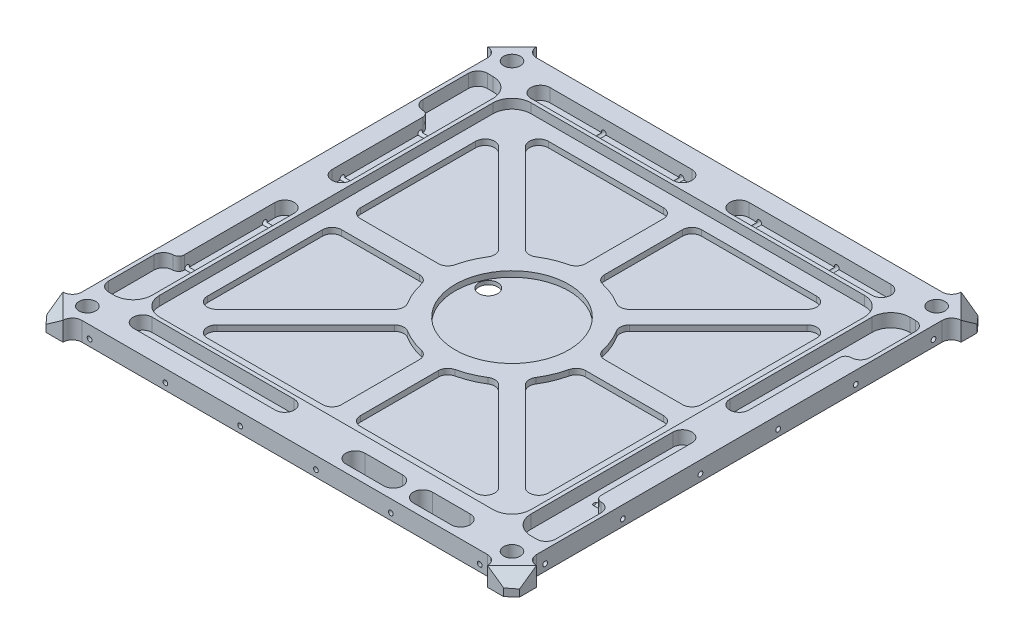
SolidWorks part; units mm, degrees
note: The reader was unsure of these and kept them because the rebuilt part matched: shared geometry of "Sketch2<6>".
ref_plane "Front" through (0, 0, 0) normal (0, 0, 1) x (1, 0, 0)
ref_plane "Top" through (0, 0, 0) normal (0, 1, 0) x (1, 0, 0)
ref_plane "Right" through (0, 0, 0) normal (1, 0, 0) x (0, 0, -1)
sketch "Sketch1" plane through (0, 0, 0) normal (0, 1, 0) x (1, 0, 0)
  line L0 (0, 125) -> (0, -125) construction
  line L1 (-125, 125) -> (125, 125)
  line L2 (-125, 125) -> (-125, -125)
  line L3 (-125, -125) -> (125, -125)
  line L4 (125, 125) -> (125, -125)
  line L5 (-125, 0) -> (125, 0) construction
  line L6 (-125, -125) -> (-112.08, -125)
  line L7 (-125, -125) -> (-125, -112.08)
  line L8 (-112.08, -125) -> (-107.08, -125)
  line L9 (-125, -125) -> (125, 125) construction
  line L10 (-125, -112.08) -> (-125, -107.08) construction
  line L11 (-107.08, -120) -> (107.08, -120)
  line L12 (-120, -107.08) -> (-120, 107.08)
  line L13 (120, -107.08) -> (120, 107.08)
  line L14 (-107.08, 120) -> (107.08, 120)
  line L15 (16.3873, 116) -> (82.4628, 116) construction
  line L16 (28.29, 116) -> (48.29, 116)
  line L17 (48.29, 111) -> (63.91, 111) construction
  line L18 (48.29, 106) -> (28.29, 106)
  line L19 (63.91, 106) -> (83.91, 106)
  line L20 (83.91, 116) -> (63.91, 116)
  line L21 (-125, 125) -> (125, -125) construction
  line L22 (-107.08, 120) -> (107.08, 120)
  line L23 (120, 107.08) -> (120, -107.08)
  line L24 (107.08, -120) -> (-107.08, -120)
  line L25 (-120, -107.08) -> (-120, 107.08)
  line L26 (63.91, -106) -> (83.91, -106)
  line L27 (83.91, -116) -> (63.91, -116)
  line L28 (28.29, -116) -> (48.29, -116)
  line L29 (48.29, -106) -> (28.29, -106)
  arc A0 (-112.08, -125) -> (-107.08, -120) centre (-107.08, -125) cw
  arc A1 (-125, -112.08) -> (-120, -107.08) centre (-125, -107.08) ccw
  arc A2 (112.08, -125) -> (107.08, -120) centre (107.08, -125) ccw
  arc A3 (125, -112.08) -> (120, -107.08) centre (125, -107.08) cw
  arc A4 (125, 112.08) -> (120, 107.08) centre (125, 107.08) ccw
  arc A5 (112.08, 125) -> (107.08, 120) centre (107.08, 125) cw
  arc A6 (-112.08, 125) -> (-107.08, 120) centre (-107.08, 125) ccw
  arc A7 (-125, 112.08) -> (-120, 107.08) centre (-125, 107.08) cw
  arc A8 (28.29, 116) -> (28.29, 106) centre (28.29, 111) ccw
  arc A9 (48.29, 106) -> (48.29, 116) centre (48.29, 111) ccw
  arc A10 (63.91, 116) -> (63.91, 106) centre (63.91, 111) ccw
  arc A11 (83.91, 106) -> (83.91, 116) centre (83.91, 111) ccw
  circle A12 centre (-22.5, 10) radius 5
  arc A13 (63.91, -116) -> (63.91, -106) centre (63.91, -111) cw
  arc A14 (83.91, -106) -> (83.91, -116) centre (83.91, -111) cw
  arc A15 (48.29, -106) -> (48.29, -116) centre (48.29, -111) cw
  arc A16 (28.29, -116) -> (28.29, -106) centre (28.29, -111) cw
  point P18 (0, -120)
  point P25 (120, 0)
  point P36 (-120, 0)
  point P50 (-112.0764, 112.0764)
  point P51 (112.0764, 112.0764)
  point P52 (112.0764, -112.0764)
  point P53 (-112.0764, -112.0764)
  dimension "D13" = 5
  dimension "D14" = 5
  dimension "D22" = 10
  dimension "D1" = 125
  dimension "D2" = 250
  dimension "D3" = 125
  dimension "D4" = 250
  dimension "D5" = 12.92
  dimension "D6" = 12.92
  dimension "D7" = 5
  dimension "D8" = 5
  dimension "D9" = 4
  dimension "D10" = 28.29
  dimension "D11" = 20
  dimension "D12" = 10
  dimension "D15" = 15.62
  dimension "D16" = 20
  dimension "D17" = 158.5
  dimension "D18" = 317
  dimension "D19" = 158.5
  dimension "D20" = 317
  dimension "D21" = 22.5
  dimension "D23" = 10
extrude "Boss-Extrude1" add sketch "Sketch1" along normal mid plane 10 contours L2 A7 L12 A1 L3 A0 L11 A2 L4 A3 L13 A4 L1 A5 L14 A6 A12 A11 L19 A10 L20 A9 L18 A8 L16 | L18 A9 L16 A8 | L19 A11 L20 A10
sketch "Sketch2" plane through (0, 5, 0) normal (0, -1, 0) x (1, 0, 0)
  line L0 (34.5597, 27.4887) -> (67.1751, 60.1041)
  line L1 (-5, 43.8748) -> (-5, 85)
  line L2 (27.4887, 34.5597) -> (60.1041, 67.1751)
  line L3 (5, 43.8748) -> (5, 85)
  line L4 (43.8748, -5) -> (85, -5)
  line L5 (43.8748, 5) -> (85, 5)
  line L6 (27.4887, -34.5597) -> (60.1041, -67.1751)
  line L7 (34.5597, -27.4887) -> (67.1751, -60.1041)
  line L8 (-5, -43.8748) -> (-5, -85)
  line L9 (5, -43.8748) -> (5, -85)
  line L10 (-34.5597, -27.4887) -> (-67.1751, -60.1041)
  line L11 (-27.4887, -34.5597) -> (-60.1041, -67.1751)
  line L12 (-43.8748, 5) -> (-85, 5)
  line L13 (-43.8748, -5) -> (-85, -5)
  line L14 (-27.4887, 34.5597) -> (-60.1041, 67.1751)
  line L15 (-34.5597, 27.4887) -> (-67.1751, 60.1041)
  line L16 (-88, 98) -> (88, 98)
  line L17 (-107.08, 120) -> (107.08, 120) construction
  line L18 (10, 90) -> (70.8579, 90)
  line L19 (-10, 90) -> (-70.8579, 90)
  line L20 (60.1041, 67.1751) -> (74.3934, 81.4645)
  line L21 (67.1751, 60.1041) -> (81.4645, 74.3934)
  line L22 (-60.1041, 67.1751) -> (-74.3934, 81.4645)
  line L23 (-67.1751, 60.1041) -> (-81.4645, 74.3934)
  line L24 (120, 107.08) -> (120, -107.08) construction
  line L25 (-120, 107.08) -> (-120, -107.08) construction
  line L26 (-98, 88) -> (-98, -88)
  line L27 (-60.1041, -67.1751) -> (-74.3934, -81.4645)
  line L28 (-90, 10) -> (-90, 70.8579)
  line L29 (-90, -10) -> (-90, -70.8579)
  line L30 (-67.1751, -60.1041) -> (-81.4645, -74.3934)
  line L31 (-88, -98) -> (88, -98)
  line L32 (98, -88) -> (98, 88)
  line L34 (-10, -90) -> (-70.8579, -90)
  line L35 (10, -90) -> (70.8579, -90)
  line L36 (90, -70.8579) -> (90, -10)
  line L37 (67.1751, -60.1041) -> (81.4645, -74.3934)
  line L38 (60.1041, -67.1751) -> (74.3934, -81.4645)
  line L39 (90, 10) -> (90, 70.8579)
  line L41 (-125, -125) -> (-125, -112.08) construction
  line L42 (-125, -125) -> (-112.08, -125) construction
  circle A0 centre (0, 0) radius 30
  arc A1 (-8.8889, 38.9998) -> (-21.2917, 33.8624) centre (0, 0) ccw
  arc A2 (5, 43.8748) -> (8.8889, 38.9998) centre (10, 43.8748) ccw
  arc A3 (-8.8889, 38.9998) -> (-5, 43.8748) centre (-10, 43.8748) ccw
  arc A4 (21.2917, 33.8624) -> (27.4887, 34.5597) centre (23.9531, 38.0953) ccw
  arc A5 (34.5597, 27.4887) -> (33.8624, 21.2917) centre (38.0953, 23.9531) ccw
  arc A6 (38.9998, 8.8889) -> (43.8748, 5) centre (43.8748, 10) ccw
  arc A7 (43.8748, -5) -> (38.9998, -8.8889) centre (43.8748, -10) ccw
  arc A8 (33.8624, -21.2917) -> (34.5597, -27.4887) centre (38.0953, -23.9531) ccw
  arc A9 (27.4887, -34.5597) -> (21.2917, -33.8624) centre (23.9531, -38.0953) ccw
  arc A10 (8.8889, -38.9998) -> (5, -43.8748) centre (10, -43.8748) ccw
  arc A11 (-5, -43.8748) -> (-8.8889, -38.9998) centre (-10, -43.8748) ccw
  arc A12 (-21.2917, -33.8624) -> (-27.4887, -34.5597) centre (-23.9531, -38.0953) ccw
  arc A13 (-34.5597, -27.4887) -> (-33.8624, -21.2917) centre (-38.0953, -23.9531) ccw
  arc A14 (-38.9998, -8.8889) -> (-43.8748, -5) centre (-43.8748, -10) ccw
  arc A15 (-43.8748, 5) -> (-38.9998, 8.8889) centre (-43.8748, 10) ccw
  arc A16 (-33.8624, 21.2917) -> (-34.5597, 27.4887) centre (-38.0953, 23.9531) ccw
  arc A17 (-27.4887, 34.5597) -> (-21.2917, 33.8624) centre (-23.9531, 38.0953) ccw
  arc A18 (-21.2917, -33.8624) -> (21.2917, -33.8624) centre (0, 0) ccw
  arc A19 (-38.9998, -8.8889) -> (-33.8624, -21.2917) centre (0, 0) ccw
  arc A20 (-33.8624, 21.2917) -> (-38.9998, 8.8889) centre (0, 0) ccw
  arc A21 (21.2917, 33.8624) -> (8.8889, 38.9998) centre (0, 0) ccw
  arc A22 (38.9998, 8.8889) -> (33.8624, 21.2917) centre (0, 0) ccw
  arc A23 (33.8624, -21.2917) -> (38.9998, -8.8889) centre (0, 0) ccw
  arc A24 (-85, -5) -> (-90, -10) centre (-85, -10) ccw
  arc A25 (-85, 5) -> (-90, 10) centre (-85, 10) cw
  arc A26 (-74.3934, 81.4645) -> (-70.8579, 90) centre (-70.8579, 85) cw
  arc A27 (-81.4645, 74.3934) -> (-90, 70.8579) centre (-85, 70.8579) ccw
  arc A28 (-5, 85) -> (-10, 90) centre (-10, 85) ccw
  arc A29 (5, 85) -> (10, 90) centre (10, 85) cw
  arc A30 (74.3934, 81.4645) -> (70.8579, 90) centre (70.8579, 85) ccw
  arc A31 (90, 70.8579) -> (81.4645, 74.3934) centre (85, 70.8579) ccw
  arc A32 (85, 5) -> (90, 10) centre (85, 10) ccw
  arc A33 (85, -5) -> (90, -10) centre (85, -10) cw
  arc A34 (81.4645, -74.3934) -> (90, -70.8579) centre (85, -70.8579) ccw
  arc A35 (74.3934, -81.4645) -> (70.8579, -90) centre (70.8579, -85) cw
  arc A36 (5, -85) -> (10, -90) centre (10, -85) ccw
  arc A37 (-5, -85) -> (-10, -90) centre (-10, -85) cw
  arc A38 (-81.4645, -74.3934) -> (-90, -70.8579) centre (-85, -70.8579) cw
  arc A39 (-74.3934, -81.4645) -> (-70.8579, -90) centre (-70.8579, -85) ccw
  arc A40 (-98, -88) -> (-88, -98) centre (-88, -88) ccw
  arc A41 (88, -98) -> (98, -88) centre (88, -88) ccw
  arc A42 (88, 98) -> (98, 88) centre (88, 88) cw
  arc A43 (-88, 98) -> (-98, 88) centre (-88, 88) ccw
  point P69 (0, 0)
  point P94 (-90, 5)
  point P101 (-5, 90)
  point P104 (5, 90)
  point P113 (90, -5)
  point P128 (-98, -98)
  point P131 (98, -98)
  point P134 (98, 98)
  point P137 (-98, 98)
  circle M131 centre (-22.5, -10) radius 5
  dimension "D1" = 60
  dimension "D2" = 80
  dimension "D5" = 10
  dimension "D6" = 10
  dimension "D9" = 8
  dimension "D15" = 5
  dimension "D18" = 10
  dimension "D3" = 10
  dimension "D4" = 5
  dimension "D7" = 8
  dimension "D8" = 22
  dimension "D10" = 8
  dimension "D11" = 196
  dimension "D12" = 22
  dimension "D13" = 22
  dimension "D14" = 22
  dimension "D16" = 8
  dimension "D17" = 8
extrude "Cut-Extrude3" cut sketch "Sketch2<6>" along normal blind 5 contours A43 L16 A42 L32 A41 L31 A40 L26 L5 A32 L39 A31 L21 L0 A5 A22 A6 L1 A28 L19 A26 L22 L14 A17 A1 A3 A0 L23 A27 L28 A25 L12 A15 A20 A16 L15 L20 A30 L18 A29 L3 A2 A21 A4 L2 | A27 L23 L15 A16 A20 A15 L12 A25 L28 | A28 L1 A3 A1 A17 L14 L22 A26 L19 | L30 A38 L29 A24 L13 A14 A19 A13 L10 | A39 L27 L11 A12 A18 A11 L8 A37 L34 | A0 M131 | A36 L9 A10 A18 A9 L6 L38 A35 L35 | A34 L37 L7 A8 A23 A7 L4 A33 L36 | A32 L5 A6 A22 A5 L0 L21 A31 L39 | A30 L20 L2 A4 A21 A2 L3 A29 L18
sketch "Sketch2<6>" plane through (0, 5, 0) normal (0, -1, 0) x (1, 0, 0) same geometry as "Sketch2"
extrude "Cut-Extrude2" cut sketch "Sketch2" along normal blind 8 contours A27 L23 L15 A16 A20 A15 L12 A25 L28 | L30 A38 L29 A24 L13 A14 A19 A13 L10 | A39 L27 L11 A12 A18 A11 L8 A37 L34 | A36 L9 A10 A18 A9 L6 L38 A35 L35 | A34 L37 L7 A8 A23 A7 L4 A33 L36 | A32 L5 A6 A22 A5 L0 L21 A31 L39 | A30 L20 L2 A4 A21 A2 L3 A29 L18 | A28 L1 A3 A1 A17 L14 L22 A26 L19 | A0 M131
sketch "Sketch3" plane through (0, 5, 0) normal (0, 1, 0) x (1, 0, 0)
  line L0 (-120, -107.08) -> (-120, 107.08) construction
  line L1 (-90, 110) -> (-15, 110)
  line L2 (-90, 110) -> (-90, 100)
  line L3 (-90, 100) -> (-15, 100)
  line L4 (-15, 110) -> (-15, 100)
  line L5 (15, 110) -> (90, 110)
  line L6 (15, 110) -> (15, 100)
  line L7 (15, 100) -> (90, 100)
  line L8 (90, 110) -> (90, 100)
  line L9 (-90, -100) -> (-15, -100)
  line L10 (-90, -100) -> (-90, -110)
  line L11 (-90, -110) -> (-15, -110)
  line L12 (-15, -100) -> (-15, -110)
  line L13 (0, 0) -> (0, 73.4679) construction
  line L14 (-118, 95) -> (-118, 71)
  line L15 (-118, -95) -> (-118, -71)
  line L16 (-100, 90) -> (-100, 60.939)
  line L17 (0, 0) -> (-171.0322, 0) construction
  line L18 (-100, -90) -> (-100, -60.939)
  line L19 (-100, 60.939) -> (-100, 15)
  line L20 (-100, -60.939) -> (-100, -15)
  line L21 (-110, 63) -> (-110, 15)
  line L22 (-110, -63) -> (-110, -15)
  line L23 (-113, 100) -> (-110, 100)
  line L24 (113, 100) -> (110, 100)
  line L25 (110, -63) -> (110, -15)
  line L26 (118, -95) -> (118, -71)
  line L27 (100, -90) -> (100, -60.939)
  line L28 (100, -60.939) -> (100, -15)
  line L29 (110, 63) -> (110, 15)
  line L30 (100, 60.939) -> (100, 15)
  line L31 (100, 90) -> (100, 60.939)
  line L32 (118, 95) -> (118, 71)
  line L33 (-113, -100) -> (-110, -100)
  line L34 (110, -100) -> (113, -100)
  line L35 (-88, 98) -> (88, 98) construction
  line L36 (-88, -98) -> (88, -98) construction
  arc A0 (-110, 15) -> (-100, 15) centre (-105, 15) ccw
  arc A1 (-113, 100) -> (-118, 95) centre (-113, 95) ccw
  arc A2 (-100, 90) -> (-110, 100) centre (-110, 90) ccw
  arc A3 (-118, 71) -> (-113, 66) centre (-113, 71) ccw
  arc A4 (-110, 63) -> (-113, 66) centre (-113, 63) ccw
  arc A5 (-110, -63) -> (-113, -66) centre (-113, -63) cw
  arc A6 (-118, -71) -> (-113, -66) centre (-113, -71) cw
  arc A7 (-113, -100) -> (-118, -95) centre (-113, -95) cw
  arc A8 (-100, -90) -> (-110, -100) centre (-110, -90) cw
  arc A9 (-110, -15) -> (-100, -15) centre (-105, -15) cw
  arc A10 (110, -63) -> (113, -66) centre (113, -63) ccw
  arc A11 (118, -71) -> (113, -66) centre (113, -71) ccw
  arc A12 (113, -100) -> (118, -95) centre (113, -95) ccw
  arc A13 (100, -90) -> (110, -100) centre (110, -90) ccw
  arc A14 (110, -15) -> (100, -15) centre (105, -15) ccw
  arc A15 (110, 15) -> (100, 15) centre (105, 15) cw
  arc A16 (110, 63) -> (113, 66) centre (113, 63) cw
  arc A17 (100, 90) -> (110, 100) centre (110, 90) cw
  arc A18 (113, 100) -> (118, 95) centre (113, 95) cw
  arc A19 (118, 71) -> (113, 66) centre (113, 71) cw
  circle A20 centre (-15, 105) radius 5
  circle A21 centre (-90, 105) radius 5
  circle A22 centre (-15, -105) radius 5
  circle A23 centre (-90, -105) radius 5
  circle A24 centre (15, 105) radius 5
  circle A25 centre (90, 105) radius 5
  dimension "D3" = 10
  dimension "D4" = 10
  dimension "D5" = 34
  dimension "D7" = 20
  dimension "D8" = 5
  dimension "D9" = 6
  dimension "D1" = 2
  dimension "D2" = 10
  dimension "D6" = 15
  dimension "D10" = 3
  dimension "D11" = 2
  dimension "D12" = 10
  dimension "D13" = 2
  dimension "D14" = 10
  dimension "D15" = 15
  dimension "D16" = 75
  dimension "D17" = 75
  dimension "D18" = 15
  dimension "D19" = 15
  dimension "D20" = 10
  dimension "D21" = 2
  dimension "D22" = 75
extrude "Cut-Extrude4" cut sketch "Sketch3" against normal blind 7 contours A4 L21 A0 L19 L16 A2 L23 A1 L14 A3 | A25 L5 A24 L7 | A19 L32 A18 L24 A17 L31 L30 A15 L29 A16 | L25 A14 L28 L27 A13 L34 A12 L26 A11 A10 | A23 L11 A22 L9 | L12 A22 | L12 A22 | L10 A23 | L10 A23 | A9 L22 A5 A6 L15 A7 L33 A8 L18 L20 | L1 L4 L3 L2 | A21 | A20
sketch "Sketch5" plane through (0, 5, 0) normal (0, 1, 0) x (1, 0, 0)
  line L0 (-125, -112.08) -> (-112.08, -125) construction
  line L1 (-125, -125) -> (-112.08, -125) construction
  arc A0 (-107.08, -120) -> (-112.08, -125) centre (-107.08, -125) ccw construction
ref_plane "Plane1" through (-61.0378, 86.3204, 61.0378) normal (-0.5, 0.7071, 0.5) x (0.8536, 0.5, 0.1464)
sketch "Sketch7" plane through (-125, 0, 0) normal (-1, 0, 0) x (0, 0, 1)
  line L0 (125, -5) -> (125, -1) construction
  line L1 (125, 5) -> (125, -5) construction
  dimension "D1" = 4
sketch "Sketch8" plane through (-61.0378, 86.3204, 61.0378) normal (-0.5, 0.7071, 0.5) x (0.8536, 0.5, 0.1464)
  line L0 (-74.8604, -87.7804) -> (-87.7804, -74.8604)
  line L1 (-87.7804, -74.8604) -> (-93.0783, -91.8949)
  line L2 (-93.0783, -91.8949) -> (-74.8604, -87.7804)
extrude "Cut-Extrude5" cut sketch "Sketch8" along normal blind 7
sketch "Sketch11" plane through (0, -5, 0) normal (0, -1, 0) x (1, 0, 0)
  line L0 (-125, 125) -> (-122.7965, 123.0104)
  line L1 (-122.7965, 123.0104) -> (-125, 120.57)
  line L2 (-125, 112.08) -> (-125, 125) construction
  line L3 (-125, 120.57) -> (-125, 125)
  line L4 (-122.7965, 123.0104) -> (-121, 125)
  line L5 (-125, 125) -> (-112.08, 125) construction
  line L6 (-121, 125) -> (-125, 125)
  line M21 (-112.08, 125) -> (-125, 125)
  line M22 (-125, 125) -> (-125, 112.08)
  dimension "D1" = 4
  dimension "D2" = 4.43
  dimension "D3" = 90
extrude "Cut-Extrude6" cut sketch "Sketch11" against normal blind 7 contours L1 L0 M22 | L0 L4 M21
sketch "Sketch13" plane through (0, 0, 0) normal (0, 0, 1) x (1, 0, 0)
  line L0 (0, 0) -> (0, 42.7136) construction
pattern_circular "CirPattern1" count 4 every 90 about axis through (0, 0, 0) along (0, 1, 0) of "Cut-Extrude5", "Cut-Extrude6"
sketch "Sketch14" plane through (0, 5, 0) normal (0, 1, 0) x (1, 0, 0)
  line L0 (-125, 112.08) -> (-112.08, 112.08) construction
  line L1 (-112.08, 125) -> (-112.08, 112.08) construction
  line L2 (112.08, 125) -> (112.08, 112.08) construction
  line L3 (112.08, 112.08) -> (125, 112.08) construction
  line L4 (112.08, -112.08) -> (125, -112.08) construction
  line L5 (112.08, -112.08) -> (112.08, -125) construction
  line L6 (-112.08, -125) -> (-112.08, -112.08) construction
  line L7 (-112.08, -112.08) -> (-125, -112.08) construction
hole_wizard "Tap Drill for M10x1.25 Tap1" positions "3DSketch1" profile "Sketch15" hole size "M10x1.25" standard "AS"
sketch3d "3DSketch1"
  point P0 (-112.08, 5, -112.08)
  point P3 (112.08, 5, -112.08)
  point P6 (112.08, 5, 112.08)
  point P9 (-112.08, 5, 112.08)
sketch "Sketch15" plane through (-112.08, 5, -112.08) normal (1, 0, 0) x (0, 0, 1)
  line L0 (0, 0) -> (0, 32.6438)
  line L1 (0, 32.6438) -> (4.4, 30)
  line L2 (4.4, 30) -> (4.4, 0)
  line L5 (4.4, 0) -> (0, 0)
  line L10 (0, 32.6438) -> (-4.4, 30) construction
  line L11 (0, -6.35) -> (0, 107.95) construction
  dimension "Hole Dia." = 8.8
  dimension "Hole Depth" = 30
  dimension "Drill Angle" = 118
sketch "Sketch16" plane through (0, -5, 0) normal (0, 1, 0) x (1, 0, 0)
  line L0 (0, 0) -> (-134.1792, 134.1792) construction
  line L1 (-134.1792, 134.1792) -> (-134.1792, 0) construction
  line L2 (-134.1792, 0) -> (0, 0) construction
  line L3 (0, 0) -> (-164.9768, 124.3189) construction
  line L4 (-110.1239, 82.9843) -> (-125.5263, 62.5445) construction
  line L5 (0, 0) -> (0, -78.4929) construction
  point P5 (-110.1239, 82.9843)
  dimension "D1" = 45
  dimension "D2" = 8
  dimension "D3" = 137.89
  dimension "D4" = 90
ref_plane "Plane2" through (-68.3198, 64.4633, -51.4827) normal (0.6378, -0.6018, 0.4806) x (-0.746, -0.6378, 0.1914)
sketch "Sketch20" plane through (-120, 0, 0) normal (-1, 0, 0) x (0, 0, 1)
  line L0 (107.08, -5) -> (-107.08, -5) construction
  line L1 (-112.08, 5) -> (-112.08, -5) construction
  circle A0 centre (-102.5, -1.5) radius 1.5
  circle A1 centre (-61.5, -1.5) radius 1.5
  circle A2 centre (-20.5, -1.5) radius 1.5
  circle A3 centre (20.5, -1.5) radius 1.5
  circle A4 centre (61.5, -1.5) radius 1.5
  circle A5 centre (102.5, -1.5) radius 1.5
  dimension "D1" = 3
  dimension "D6" = 3
  dimension "D8" = 3
  dimension "D10" = 3.5
  dimension "D11" = 3
  dimension "D13" = 3
  dimension "D15" = 3.5
  dimension "D16" = 3
  dimension "D2" = 3.5
  dimension "D3" = 9.58
  dimension "D4" = 41
  dimension "D5" = 3.5
  dimension "D7" = 41
  dimension "D9" = 3.5
  dimension "D12" = 41
  dimension "D14" = 41
  dimension "D17" = 3.5
  dimension "D18" = 41
hole_wizard "M3x0.5 Tapped Hole1" positions "Sketch22" profile "Sketch21" tap size "M3x0.5" standard "ANSI Metric"
sketch "Sketch22" plane through (-120, 0, 0) normal (-1, 0, 0) x (0, 0, 1)
  point P0 (-102.5, -1.5)
  point P3 (-61.5, -1.5)
  point P6 (-20.5, -1.5)
  point P9 (20.5, -1.5)
  point P12 (61.5, -1.5)
  point P15 (102.5, -1.5)
sketch "Sketch21" plane through (-120, -1.5, -102.5) normal (0, 1, 0) x (0, 0, 1)
  line L0 (0, 0) -> (0, 15.7511)
  line L1 (0, 15.7511) -> (1.25, 15)
  line L2 (1.25, 15) -> (1.25, 0)
  line L5 (1.25, 0) -> (0, 0)
  line L10 (0, 15.7511) -> (-1.25, 15) construction
  line L11 (0, -6.35) -> (0, 107.95) construction
  dimension "Tap Drill Dia." = 2.5
  dimension "Tap Drill Depth" = 15
  dimension "Drill Angle" = 118
cosmetic thread "Hole Thread1" parameters "D1"=10, "D2"=3
cosmetic thread "Hole Thread2" parameters "D1"=10, "D2"=3
cosmetic thread "Hole Thread3" parameters "D1"=10, "D2"=3
cosmetic thread "Hole Thread4" parameters "D1"=10, "D2"=3
cosmetic thread "Hole Thread5" parameters "D1"=10, "D2"=3
cosmetic thread "Hole Thread6" parameters "D1"=10, "D2"=3
hole_wizard "M3x0.5 Tapped Hole2" positions "Sketch24" profile "Sketch23" tap size "M3x0.5" standard "ANSI Metric"
sketch "Sketch24" plane through (0, 0, 120) normal (0, 0, 1) x (1, 0, 0)
  line L1 (-107.08, -5) -> (107.08, -5) construction
  line L2 (-112.08, 5) -> (-112.08, -5) construction
  point P0 (-103, -1.5)
  point P7 (-63, -1.5)
  point P9 (-23.5, -1.5)
  point P11 (16.5, -1.5)
  point P13 (56, -1.5)
  point P15 (103, -1.5)
  dimension "D1" = 9.08
  dimension "D2" = 3.5
  dimension "D3" = 40
  dimension "D4" = 39.5
  dimension "D5" = 40
  dimension "D6" = 39.5
  dimension "D7" = 47
sketch "Sketch23" plane through (-103, -1.5, 120) normal (1, 0, 0) x (0, -1, 0)
  line L0 (0, 0) -> (0, 15.7511)
  line L1 (0, 15.7511) -> (1.25, 15)
  line L2 (1.25, 15) -> (1.25, 0)
  line L5 (1.25, 0) -> (0, 0)
  line L10 (0, 15.7511) -> (-1.25, 15) construction
  line L11 (0, -6.35) -> (0, 107.95) construction
  dimension "Tap Drill Dia." = 2.5
  dimension "Tap Drill Depth" = 15
  dimension "Drill Angle" = 118
cosmetic thread "Hole Thread7" parameters "D1"=10, "D2"=3
cosmetic thread "Hole Thread8" parameters "D1"=10, "D2"=3
cosmetic thread "Hole Thread9" parameters "D1"=10, "D2"=3
cosmetic thread "Hole Thread10" parameters "D1"=10, "D2"=3
cosmetic thread "Hole Thread11" parameters "D1"=10, "D2"=3
cosmetic thread "Hole Thread12" parameters "D1"=10, "D2"=3
hole_wizard "M3x0.5 Tapped Hole3" positions "Sketch26" profile "Sketch25" tap size "M3x0.5" standard "ANSI Metric"
sketch "Sketch26" plane through (120, 0, 0) normal (1, 0, 0) x (0, 0, -1)
  line L0 (-112.08, 5) -> (-112.08, -5) construction
  line L1 (-107.08, -5) -> (107.08, -5) construction
  point P0 (-102.5, -1.5)
  point P8 (-61.5, -1.5)
  point P10 (-20.5, -1.5)
  point P12 (20.5, -1.5)
  point P14 (61.5, -1.5)
  point P16 (102.5, -1.5)
  dimension "D1" = 9.58
  dimension "D2" = 3.5
  dimension "D3" = 41
  dimension "D4" = 41
  dimension "D5" = 41
  dimension "D6" = 41
  dimension "D7" = 41
  dimension "D8" = 3.5
sketch "Sketch25" plane through (120, -1.5, 102.5) normal (0, 1, 0) x (0, 0, -1)
  line L0 (0, 0) -> (0, 15.7511)
  line L1 (0, 15.7511) -> (1.25, 15)
  line L2 (1.25, 15) -> (1.25, 0)
  line L5 (1.25, 0) -> (0, 0)
  line L10 (0, 15.7511) -> (-1.25, 15) construction
  line L11 (0, -6.35) -> (0, 107.95) construction
  dimension "Tap Drill Dia." = 2.5
  dimension "Tap Drill Depth" = 15
  dimension "Drill Angle" = 118
cosmetic thread "Hole Thread19" parameters "D1"=10, "D2"=3
cosmetic thread "Hole Thread20" parameters "D1"=10, "D2"=3
cosmetic thread "Hole Thread21" parameters "D1"=10, "D2"=3
cosmetic thread "Hole Thread22" parameters "D1"=10, "D2"=3
cosmetic thread "Hole Thread23" parameters "D1"=10, "D2"=3
cosmetic thread "Hole Thread24" parameters "D1"=10, "D2"=3
hole_wizard "M3x0.5 Tapped Hole4" positions "Sketch28" profile "Sketch27" tap size "M3x0.5" standard "ANSI Metric"
sketch "Sketch28" plane through (0, 0, -120) normal (0, 0, -1) x (-1, 0, 0)
  line L0 (-112.08, 5) -> (-112.08, -5) construction
  line L1 (107.08, -5) -> (-107.08, -5) construction
  point P0 (-102.5, -1.5)
  point P2 (-102.5, -1.5)
  point P9 (-61.5, -1.5)
  point P11 (-20.5, -1.5)
  point P13 (20.5, -1.5)
  point P15 (61.5, -1.5)
  point P19 (102.5, -1.5)
  dimension "D1" = 9.58
  dimension "D2" = 3.5
  dimension "D3" = 41
  dimension "D4" = 41
  dimension "D5" = 41
  dimension "D6" = 41
  dimension "D7" = 41
sketch "Sketch27" plane through (102.5, -1.5, -120) normal (1, 0, 0) x (0, 1, 0)
  line L0 (0, 0) -> (0, 15.7511)
  line L1 (0, 15.7511) -> (1.25, 15)
  line L2 (1.25, 15) -> (1.25, 0)
  line L5 (1.25, 0) -> (0, 0)
  line L10 (0, 15.7511) -> (-1.25, 15) construction
  line L11 (0, -6.35) -> (0, 107.95) construction
  dimension "Tap Drill Dia." = 2.5
  dimension "Tap Drill Depth" = 15
  dimension "Drill Angle" = 118
cosmetic thread "Hole Thread25" parameters "D1"=10, "D2"=3
cosmetic thread "Hole Thread26" parameters "D1"=10, "D2"=3
cosmetic thread "Hole Thread27" parameters "D1"=10, "D2"=3
cosmetic thread "Hole Thread28" parameters "D1"=10, "D2"=3
cosmetic thread "Hole Thread29" parameters "D1"=10, "D2"=3
cosmetic thread "Hole Thread30" parameters "D1"=10, "D2"=3
cosmetic thread "Hole Thread32" parameters "D1"=10, "D2"=3
